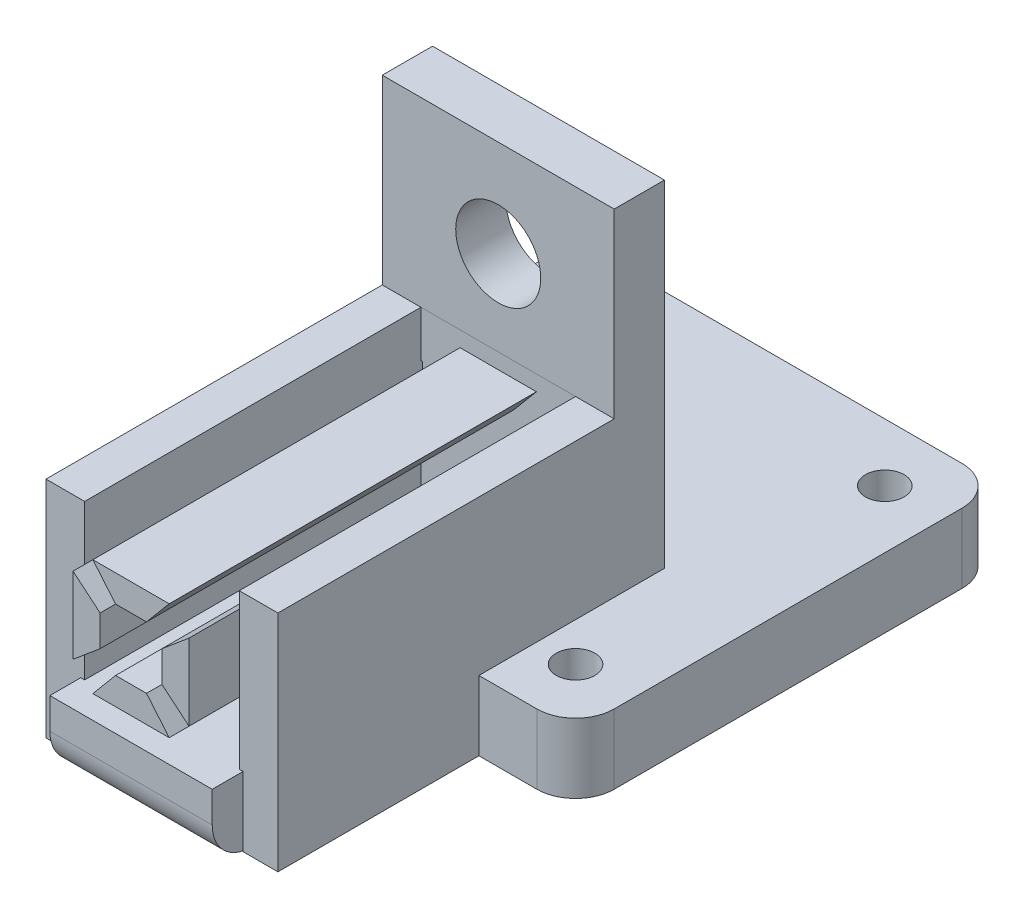
SolidWorks part; units mm, degrees
ref_plane "Front Plane" through (0, 0, 0) normal (0, 0, 1) x (1, 0, 0)
ref_plane "Top Plane" through (0, 0, 0) normal (0, 1, 0) x (1, 0, 0)
ref_plane "Right Plane" through (0, 0, 0) normal (1, 0, 0) x (0, 0, -1)
sketch "Sketch1" plane through (0, 0, 0) normal (0, 1, 0) x (1, 0, 0)
  line L0 (27.5, 55) -> (27.5, 0) construction
  line L1 (5, 0) -> (50, 0)
  line L2 (0, 5) -> (0, 50)
  line L3 (5, 55) -> (50, 55)
  line L4 (55, 5) -> (55, 50)
  line L5 (0, 55) -> (7.5, 55) construction
  line L6 (0, 55) -> (0, 47.5) construction
  line L7 (0, 47.5) -> (7.5, 47.5) construction
  line L8 (7.5, 55) -> (7.5, 47.5) construction
  line L9 (0, 27.5) -> (55, 27.5) construction
  circle A0 centre (7.5, 47.5) radius 2.5
  circle A1 centre (47.5, 47.5) radius 2.5
  circle A2 centre (47.5, 7.5) radius 2.5
  circle A3 centre (7.5, 7.5) radius 2.5
  arc A4 (50, 0) -> (55, 5) centre (50, 5) ccw
  arc A5 (50, 55) -> (55, 50) centre (50, 50) cw
  arc A6 (0, 50) -> (5, 55) centre (5, 50) cw
  arc A7 (5, 0) -> (0, 5) centre (5, 5) cw
  point P23 (55, 55)
  point P29 (0, 0)
  dimension "D3" = 2
  dimension "D5" = 5
  dimension "D1" = 55
  dimension "D2" = 55
  dimension "D4" = 2
extrude "Boss-Extrude2" add sketch "Sketch1" along normal blind 8 and the other way blind 1
sketch "Sketch2" plane through (0, 8, 0) normal (0, 1, 0) x (1, 0, 0)
  line L0 (0, 27.5) -> (55, 27.5)
  line L1 (0, 50) -> (0, 5) construction
  line L2 (55, 5) -> (55, 50) construction
  line L4 (0, 27.5) -> (55, 27.5)
  line L5 (0, 27.5) -> (0, 55)
  line L6 (0, 55) -> (55, 55)
  line L7 (55, 27.5) -> (55, 55)
  dimension "D1" = 27.5
sketch "Sketch5" plane through (0, 8, 0) normal (0, 1, 0) x (1, 0, 0)
  line L0 (27.5, 27.5) -> (27.5, 0)
  line L2 (5, 0) -> (50, 0) construction
  line L3 (27.5, 27.5) -> (27.5, 24)
  line L5 (27.5, 24) -> (23, 24)
  line L6 (27.5, 24) -> (27.5, 17.5)
  line L7 (27.5, 17.5) -> (23, 17.5)
  line L8 (23, 24) -> (23, 17.5)
  line L9 (27.5, 24) -> (32, 24)
  line L10 (27.5, 24) -> (27.5, 17.5)
  line L11 (27.5, 17.5) -> (32, 17.5)
  line L12 (32, 24) -> (32, 17.5)
  dimension "D1" = 3.5
  dimension "D2" = 6.5
  dimension "D3" = 4.5
  dimension "D4" = 4.5
  dimension "D5" = 6.5
extrude "Boss-Extrude3" add sketch "Sketch5" along normal blind 14.5 contours L5 L8 L7 L0 | L12 L9 L0 L11 region at (29.75, 8, -20.75) region at (25.25, 8, -20.75)
sketch "Sketch6" plane through (0, 0, -24) normal (0, 0, -1) x (-1, 0, 0)
  line L0 (-27.5, 8) -> (-27.5, 17)
  line L1 (-32, 8) -> (-23, 8) construction
  circle A0 centre (-27.5, 17) radius 4
  dimension "D2" = 8
  dimension "D1" = 9
extrude "Cut-Extrude4" cut sketch "Sketch6" against normal blind 1.5 contours A0 region at (24.7516, 14.2516, -24)
sketch "Sketch11" plane through (0, 0, -24) normal (0, 0, -1) x (-1, 0, 0)
  line L0 (-27.5, 22.5) -> (-25.5, 22.5)
  line L1 (-32.4368, 26) -> (-22.5632, 26)
  line L2 (-32, 22.5) -> (-23, 22.5) construction
  line L3 (-25.5, 22.5) -> (-27.5, 22.5)
  line L4 (-25.5, 22.5) -> (-29.5, 22.5)
  line L5 (-25.5, 22.5) -> (-25.5, 26)
  line L6 (-25.5, 26) -> (-29.5, 26)
  line L7 (-29.5, 22.5) -> (-29.5, 26)
  line L8 (-22.5632, 26) -> (-25.5, 22.5)
  line L9 (-29.5, 22.5) -> (-32.4368, 26)
  point P10 (-27.5, 26)
  line M9 (-23, 22.5) -> (-32, 22.5)
  dimension "D1" = 2
  dimension "D2" = 4
  dimension "D3" = 3.5
  dimension "D4" = 40
sketch "Sketch12" plane through (0, 8, 0) normal (0, 1, 0) x (1, 0, 0)
  line L0 (27.5, 17.5) -> (27.5, 0)
  line L1 (32, 17.5) -> (23, 17.5) construction
  line L2 (5, 0) -> (50, 0) construction
  line L3 (17, 0) -> (17, -30)
  line L4 (17, 0) -> (38, 0)
  line L5 (27.5, 0) -> (27.5, -30)
  line L6 (17, -30) -> (38, -30)
  line L7 (38, 0) -> (38, -30)
  point P9 (23.9675, 0)
  line M9 (5, 0) -> (50, 0)
  dimension "D1" = 30
  dimension "D2" = 10.5
extrude "Boss-Extrude7" add sketch "Sketch12" against normal blind 9 contours L7 L5 L6 M9 | L3 L6 L5 M9 region at (22.25, 8, 15) region at (32.75, 8, 15)
sketch "Sketch15" plane through (0, 22.5, 0) normal (0, 1, 0) x (1, 0, 0)
  line L0 (32, 24) -> (32, 17.5) construction
  line L1 (32, 17.5) -> (23, 17.5)
  line L2 (32, 17.5) -> (32, 24)
  line L3 (32, 24) -> (23, 24)
  line L4 (23, 17.5) -> (23, 24)
  line L5 (32, 17.5) -> (23, 17.5) construction
extrude "Boss-Extrude8" add sketch "Sketch15" along normal blind 3.5
extrude "Boss-Extrude9" add sketch "Sketch11" against normal blind 54 contours L9 L7 L1 | L7 L5 L1 M9 | L8 L1 L5 region at (27.5, 24.25, -24) region at (24.5211, 24.8333, -24) region at (30.4789, 24.8333, -24)
fillet "Fillet4" radius 5 1 edges at (27.5, -1, 30)
sketch "Sketch18" plane through (0, 26, 0) normal (0, 1, 0) x (1, 0, 0)
  line L0 (32.4368, -30) -> (32.4368, 24) construction
  line L1 (22.5632, 24) -> (32.4368, 24)
  line L2 (22.5632, 24) -> (22.5632, 17.5)
  line L3 (22.5632, 17.5) -> (32.4368, 17.5)
  line L4 (32.4368, 24) -> (32.4368, 17.5)
  dimension "D1" = 6.5
extrude "Boss-Extrude11" add sketch "Sketch18" along normal blind 0.5
sketch "Sketch20" plane through (0, 8, 0) normal (0, 1, 0) x (1, 0, 0)
  line L0 (27.5, -1030) -> (27.5, 48970) construction
  line L1 (17, -30) -> (38, -30) construction
  line L2 (32, 17.5) -> (23, 17.5) construction
  line L3 (27.5, 17.5) -> (16.5, 17.5)
  line L4 (27.5, 17.5) -> (27.5, 0)
  line L5 (27.5, 0) -> (16.5, 0)
  line L6 (16.5, 17.5) -> (16.5, 0)
  line L7 (27.5, 17.5) -> (16.5, 0) construction
  line L8 (27.5, 0) -> (16.5, 17.5) construction
  line L10 (27.5, 17.5) -> (38.5, 17.5)
  line L11 (27.5, 17.5) -> (27.5, 0)
  line L12 (27.5, 0) -> (38.5, 0)
  line L13 (38.5, 17.5) -> (38.5, 0)
  line L14 (27.5, 17.5) -> (38.5, 0) construction
  line L15 (27.5, 0) -> (38.5, 17.5) construction
  line L16 (38.5, 17.5) -> (42.5, 17.5)
  line L17 (38.5, 17.5) -> (38.5, 0)
  line L18 (38.5, 0) -> (42.5, 0)
  line L19 (42.5, 17.5) -> (42.5, 0)
  line L21 (16.5, 17.5) -> (12.5, 17.5)
  line L22 (16.5, 17.5) -> (16.5, 0)
  line L23 (16.5, 0) -> (12.5, 0)
  line L24 (12.5, 17.5) -> (12.5, 0)
  line L26 (42.5, 0) -> (38.5, 0)
  line L27 (42.5, 0) -> (42.5, 17.5)
  line L28 (42.5, 17.5) -> (38.5, 17.5)
  line L29 (38.5, 0) -> (38.5, 17.5)
  line L30 (16.5, 0) -> (12.5, 0)
  line L31 (16.5, 0) -> (16.5, 17.5)
  line L32 (16.5, 17.5) -> (12.5, 17.5)
  line L33 (12.5, 0) -> (12.5, 17.5)
  point P5 (27.5, -30)
  point P9 (22, 8.75)
  point P14 (33, 8.75)
  line M12 (5, 0) -> (17, 0)
  line M16 (38, 0) -> (50, 0)
  dimension "D2" = 11
  dimension "D3" = 17.5
  dimension "D4" = 4
extrude "Boss-Extrude12" add sketch "Sketch20" along normal blind 18 contours L21 L24 L6 M12 | L19 L16 L13 M16 region at (14.5, 8, -8.75) region at (40.5, 8, -8.75)
sketch "Sketch21" plane through (12.5, 0, 0) normal (-1, 0, 0) x (0, 0, 1)
  line L0 (-17.5, 26) -> (-17.5, 8) construction
  line L1 (0, 26) -> (-17.5, 26)
  line L2 (0, 26) -> (0, 24)
  line L3 (0, 24) -> (-17.5, 24)
  line L4 (-17.5, 26) -> (-17.5, 24)
  dimension "D1" = 2
sketch "Sketch22" plane through (12.5, 0, 0) normal (-1, 0, 0) x (0, 0, 1)
  line L1 (-17.5, 24) -> (0, 24)
  line L2 (-17.5, 24) -> (-17.5, 28)
  line L3 (-17.5, 28) -> (0, 28)
  line L4 (0, 24) -> (0, 28)
  dimension "D1" = 4
extrude "Boss-Extrude13" add sketch "Sketch22" along normal blind 11 and the other way blind 4 contours L3 L4 L1 L2
sketch "Sketch25" plane through (0, 28, 0) normal (0, 1, 0) x (1, 0, 0)
  line L2 (1.5, 17.5) -> (16.5, 17.5) construction
  line L3 (1.5, 0) -> (3.5, 0)
  line L4 (1.5, 0) -> (1.5, 17.5)
  line L5 (1.5, 17.5) -> (3.5, 17.5)
  line L6 (3.5, 0) -> (3.5, 17.5)
  dimension "D1" = 2
extrude "Boss-Extrude14" add sketch "Sketch25" along normal blind 41
sketch "Sketch28" plane through (1.5, 0, 0) normal (-1, 0, 0) x (0, 0, 1)
  line L2 (0, 69) -> (-41, 69)
  line L3 (0, 69) -> (0, 24)
  line L4 (0, 24) -> (-41, 24)
  line L5 (-41, 69) -> (-41, 24)
  dimension "D1" = 45
  dimension "D2" = 41
extrude "Boss-Extrude15" add sketch "Sketch28" against normal blind 2
sketch "Sketch29" plane through (1.5, 0, 0) normal (-1, 0, 0) x (0, 0, 1)
  line L1 (0, 24) -> (-5, 24)
  line L2 (0, 24) -> (0, 33)
  line L3 (0, 33) -> (-5, 33)
  line L4 (-5, 24) -> (-5, 33)
  circle A0 centre (-5, 33) radius 1.75
  circle A1 centre (-36, 33) radius 1.75
  circle A2 centre (-36, 64) radius 1.75
  circle A3 centre (-5, 64) radius 1.75
  dimension "D3" = 3.5
  dimension "D6" = 31
  dimension "D1" = 9
  dimension "D2" = 5
  dimension "D7" = 31
  dimension "D4" = 2
  dimension "D5" = 2
extrude "Cut-Extrude8" cut sketch "Sketch29" against normal blind 9 contours A1 | A3 | A0 | A2 region at (1.5, 33, -36) region at (1.5, 64, -5)
sketch "Sketch30" plane through (42.5, 0, 0) normal (1, 0, 0) x (0, 0, -1)
  line L0 (17.5, 26) -> (17.5, 8) construction
  line L1 (0, 26) -> (17.5, 26)
  line L2 (0, 26) -> (0, 24)
  line L3 (0, 24) -> (17.5, 24)
  line L4 (17.5, 26) -> (17.5, 24)
  line L6 (0, 24) -> (17.5, 24)
  line L7 (0, 24) -> (0, 28)
  line L8 (0, 28) -> (17.5, 28)
  line L9 (17.5, 24) -> (17.5, 28)
  line M4 (17.5, 8) -> (17.5, 26)
  line M5 (17.5, 26) -> (0, 26)
  line M6 (0, 26) -> (0, 8)
  dimension "D1" = 2
  dimension "D2" = 4
extrude "Boss-Extrude16" add sketch "Sketch30" along normal blind 9 and the other way blind 4 contours L3 M6 M4 M5 | L9 L8 L7 M5 region at (42.5, 27, -8.75) region at (42.5, 25, -8.75)
sketch "Sketch31" plane through (3.5, 0, 0) normal (1, 0, 0) x (0, 0, -1)
  line L1 (41, 69) -> (20.5, 69)
  line L2 (41, 69) -> (41, 47)
  line L3 (41, 47) -> (20.5, 47)
  line L4 (20.5, 69) -> (20.5, 47)
  circle A0 centre (20.5, 47) radius 10
  dimension "D3" = 20
  dimension "D1" = 22
  dimension "D2" = 20.5
extrude "Cut-Extrude9" cut sketch "Sketch31" against normal blind 9 contours L4 A0 L3 | L3 A0 L4 region at (3.5, 51.2441, -24.7441) region at (3.5, 45.5853, -19.0853)
sketch "Sketch32" plane through (0, 0, -17.5) normal (0, 0, -1) x (-1, 0, 0)
  line L1 (-16.5, 28) -> (-3.5, 28)
  line L2 (-16.5, 28) -> (-16.5, 24)
  line L3 (-16.5, 24) -> (-3.5, 24)
  line L4 (-3.5, 28) -> (-3.5, 24)
extrude "Boss-Extrude17" add sketch "Sketch32" along normal blind 23.5
sketch "Sketch33" plane through (0, 8, 0) normal (0, 1, 0) x (1, 0, 0)
  line L0 (38.5, 17.5) -> (38.5, 0)
  line L1 (38.5, 17.5) -> (38, 17.5)
  line L2 (38.5, 0) -> (38, 0)
  line L3 (38, 17.5) -> (38, 0)
  line L4 (16.5, 17.5) -> (16.5, 0)
  line L5 (16.5, 17.5) -> (17, 17.5)
  line L6 (16.5, 0) -> (17, 0)
  line L7 (17, 17.5) -> (17, 0)
  dimension "D1" = 0.5
  dimension "D2" = 0.5
extrude "Boss-Extrude18" add sketch "Sketch33" along normal blind 20
sketch "Sketch34" plane through (0, 0, 0) normal (0, 0, 1) x (1, 0, 0)
  line L0 (42.5, 24) -> (42.5, 8) construction
  line L1 (51.5, 28) -> (42.5, 28)
  line L2 (51.5, 28) -> (51.5, 24)
  line L3 (51.5, 24) -> (42.5, 24)
  line L4 (42.5, 28) -> (42.5, 24)
  line L5 (42.5, 24) -> (51.5, 24) construction
  line L7 (42.5, 28) -> (38, 28)
  line L8 (42.5, 28) -> (42.5, -1)
  line L9 (42.5, -1) -> (38, -1)
  line L10 (38, 28) -> (38, -1)
  line L11 (17, 28) -> (1.5, 28)
  line L12 (17, 28) -> (17, 24)
  line L13 (17, 24) -> (1.5, 24)
  line L14 (1.5, 28) -> (1.5, 24)
  line L15 (12.5, 24) -> (17, 24)
  line L16 (12.5, 24) -> (12.5, -1)
  line L17 (12.5, -1) -> (17, -1)
  line L18 (17, 24) -> (17, -1)
  line M1 (42.5, 8) -> (42.5, 24)
  line M2 (42.5, 24) -> (51.5, 24)
  line M3 (51.5, 24) -> (51.5, 28)
  line M4 (51.5, 28) -> (38, 28)
  line M5 (38, 28) -> (38, 8)
  line M6 (38, 8) -> (38, -1)
  line M7 (38, -1) -> (50, -1)
extrude "Boss-Extrude19" add sketch "Sketch34" along normal blind 26 contours L18 L13 L16 L17 | L11 L14 L13 L12 | L8 L4 M1 M4 M5 M6 M7 | L4 M4 M2 M3 region at (47, 26, 0) region at (40.25, 13.5, 0) region at (9.25, 26, 0) region at (14.75, 11.5, 0)
sketch "Sketch35" plane through (0, 0, -17.5) normal (0, 0, 1) x (1, 0, 0)
  line L1 (32.4368, 26.5) -> (22.5632, 26.5)
  line L2 (32.4368, 26.5) -> (32.4368, 26)
  line L3 (32.4368, 26) -> (22.5632, 26)
  line L4 (22.5632, 26.5) -> (22.5632, 26)
extrude "Boss-Extrude20" add sketch "Sketch35" along normal blind 47.5
sketch "Sketch37" plane through (0, 0, -17.5) normal (0, 0, 1) x (1, 0, 0)
  line L0 (27.5, 8) -> (29.5, 8)
  line L2 (32, 8) -> (23, 8) construction
  line L3 (29.5, 12) -> (33.1362, 7.6666)
  line L4 (29.5, 8) -> (25.5, 8)
  line L5 (29.5, 8) -> (29.5, 12)
  line L6 (29.5, 12) -> (25.5, 12)
  line L7 (25.5, 8) -> (25.5, 12)
  line L8 (25.5, 12) -> (21.8638, 7.6666)
  line L9 (21.8638, 7.6666) -> (33.1362, 7.6666)
  line M8 (32, 8) -> (32, 25.4794)
  line M12 (23, 25.4794) -> (23, 8)
  line M13 (23, 8) -> (32, 8)
  dimension "D1" = 2
  dimension "D2" = 4
  dimension "D3" = 4
  dimension "D4" = 40
  dimension "D5" = 40
extrude "Boss-Extrude21" add sketch "Sketch37" along normal blind 47.5 contours L7 L8 M12 M13 | L7 L5 L6 M13 | L5 L3 M13 M8 | L8 L9 L3 M8 M13 M12 region at (27.5, 10, -17.5) region at (27.5, 7.9298, -17.5) region at (30.5027, 9.4025, -17.5) region at (24.4973, 9.4025, -17.5)
sketch "Sketch38" plane through (0, 0, 30) normal (0, 0, 1) x (1, 0, 0)
  line L1 (22.5632, 26.5) -> (22.1436, 26.5)
  line L2 (22.5632, 26.5) -> (22.5632, 8)
  line L3 (22.5632, 8) -> (22.1436, 8)
  line L4 (22.1436, 26.5) -> (22.1436, 8)
  line L5 (32.4368, 26.5) -> (32.8564, 26.5)
  line L6 (32.4368, 26.5) -> (32.4368, 8)
  line L7 (32.4368, 8) -> (32.8564, 8)
  line L8 (32.8564, 26.5) -> (32.8564, 8)
extrude "Cut-Extrude10" cut sketch "Sketch38" against normal blind 90.5
sketch "Sketch39" plane through (0, 0, 30) normal (0, 0, 1) x (1, 0, 0)
  line L0 (27.784, 26.1035) -> (27.5, 26.5)
  line L1 (32.4368, 26.5) -> (38, 26.5)
  line L2 (32.4368, 26.5) -> (32.4368, 8)
  line L3 (32.4368, 8) -> (38, 8)
  line L4 (38, 26.5) -> (38, 8)
  line L5 (32.4368, 26.5) -> (22.5632, 26.5) construction
  line L6 (27.5, 26.5) -> (27.5, 8)
  line L7 (38, 17.25) -> (38, 19.25)
  line L8 (34, 19.25) -> (38, 22.6064)
  line L9 (38, 19.25) -> (34, 19.25)
  line L10 (38, 19.25) -> (38, 15.25)
  line L11 (38, 15.25) -> (34, 15.25)
  line L12 (34, 19.25) -> (34, 15.25)
  line L13 (34, 15.25) -> (38, 11.8936)
  line L14 (22.5632, 8.5) -> (21.9673, 8)
  line L15 (17, 8) -> (22.5632, 8) construction
  line L16 (17, 22.6064) -> (17.7151, 22.6064)
  line L17 (38, 22.6064) -> (37.2849, 22.6064)
  line L18 (38, 22.6064) -> (38, 22.0064)
  line L19 (38, 22.0064) -> (37.2849, 22.0064)
  line L20 (37.2849, 22.6064) -> (37.2849, 22.0064)
  line L21 (38, 11.8936) -> (37.2849, 11.8936)
  line L22 (38, 11.8936) -> (38, 12.4936)
  line L23 (38, 12.4936) -> (37.2849, 12.4936)
  line L24 (37.2849, 11.8936) -> (37.2849, 12.4936)
  line L25 (17.7151, 22.6064) -> (17.7151, 22.0064)
  line L26 (17, 22.0064) -> (17.7151, 22.0064)
  line L27 (21, 19.25) -> (17, 22.6064)
  line L28 (21, 19.25) -> (21, 15.25)
  line L29 (17, 19.25) -> (21, 19.25)
  line L30 (17.7151, 11.8936) -> (17.7151, 12.4936)
  line L31 (17, 11.8936) -> (17.7151, 11.8936)
  line L32 (17, 12.4936) -> (17.7151, 12.4936)
  line L33 (17, 26.5) -> (17, 8)
  line L34 (17, 15.25) -> (21, 15.25)
  line L35 (21, 15.25) -> (17, 11.8936)
  line L36 (17, 19.25) -> (17, 22.0064)
  line L37 (17, 22.0064) -> (17.7151, 22.0064)
  line L38 (17.7151, 22.0064) -> (21, 19.25)
  line L39 (17, 19.25) -> (21, 19.25)
  dimension "D1" = 2
  dimension "D2" = 4
  dimension "D3" = 4
  dimension "D4" = 40
  dimension "D5" = 40
  dimension "D6" = 0.6
  dimension "D7" = 0.6
extrude "Boss-Extrude23" add sketch "Sketch39" against normal blind 47.5 contours L26 L33 L29 L27 | L33 L34 L28 L29 | L35 L34 L33 L32 | L23 L4 L11 L13 | L9 L12 L11 L4 | L4 L19 L8 L9 region at (36.6305, 20.3081, 30) region at (36, 17.25, 30) region at (36.6305, 14.1919, 30) region at (18.3695, 20.3081, 30) region at (19, 17.25, 30) region at (18.3695, 14.1919, 30)
ref_plane "Plane1" through (5, 8, 0) normal (0, 1, 0) x (1, 0, 0)
sketch "Sketch48" plane through (0, 8, 0) normal (0, 1, 0) x (1, 0, 0)
  line L1 (7.5, 24) -> (47.5, 24)
  line L3 (7.5, 17.5) -> (47.5, 17.5)
  line L7 (7.5, 17.5) -> (7.5, 24)
  line L15 (47.5, 24) -> (47.5, 17.5)
  line M3 (12.5, 17.5) -> (17, 17.5)
  line M8 (22.5632, 17.5) -> (23, 17.5)
  line M9 (23, 17.5) -> (23, 24)
  line M11 (32, 24) -> (32, 17.5)
  line M12 (32, 17.5) -> (32.4368, 17.5)
  line M17 (38, 17.5) -> (42.5, 17.5)
sketch "Sketch49" plane through (0, 0, -24) normal (0, 0, -1) x (-1, 0, 0)
  line L0 (-17.5, 3.5) -> (-27.5, 17)
  line L1 (-27.5, 17) -> (-17.5, 17)
  line L2 (-17.5, 17) -> (-17.5, 3.5)
  line L3 (-27.5, 17) -> (-37.5, 3.5)
  line L4 (-37.5, 3.5) -> (-37.5, 17)
  line L5 (-37.5, 17) -> (-27.5, 17)
  circle A0 centre (-37.5, 17) radius 4
  circle A1 centre (-17.5, 17) radius 4
  dimension "D1" = 8
  dimension "D2" = 8
extrude "Boss-Extrude31" add sketch "Sketch48" along normal blind 18.5 contours M12 M17 M11 | L15 | M8 M9 M3 | L7 region at (15.25, 8, -20.75) region at (39.75, 8, -20.75)
sketch "Sketch51" plane through (0, 0, -24) normal (0, 0, -1) x (-1, 0, 0)
  line L1 (-32.4593, 12.5515) -> (-22.8331, 12.5515)
  line L2 (-32.4593, 12.5515) -> (-32.4593, 21.6767)
  line L3 (-32.4593, 21.6767) -> (-22.8331, 21.6767)
  line L4 (-22.8331, 12.5515) -> (-22.8331, 21.6767)
extrude "Boss-Extrude32" add sketch "Sketch51" against normal blind 1.5
sketch "Sketch53" plane through (0, 0, -24) normal (0, 0, -1) x (-1, 0, 0)
  line L0 (-27.5, 17) -> (-27.5, 8)
  line L1 (-47.5, 8) -> (-7.5, 8) construction
  line L2 (-27.5, 8) -> (-27.5, 26.5)
  line L3 (-47.5, 26.5) -> (-16.5, 26.5) construction
  line L4 (-27.5, 17.25) -> (-23.5, 17.25)
  line L5 (-23.5, 17.25) -> (-31.5, 17.25)
  line L7 (-31.5, 13.25) -> (-23.5, 13.25)
  line L8 (-31.5, 13.25) -> (-31.5, 21.25)
  line L9 (-31.5, 21.25) -> (-23.5, 21.25)
  line L10 (-23.5, 13.25) -> (-23.5, 21.25)
  line L11 (-31.5, 13.25) -> (-23.5, 21.25) construction
  line L12 (-31.5, 21.25) -> (-23.5, 13.25) construction
  dimension "D1" = 4
  dimension "D2" = 4
  dimension "D3" = 8
  dimension "D4" = 8
sketch "Sketch54" plane through (0, 0, -17.5) normal (0, 0, 1) x (1, 0, 0)
  line L0 (27.5, 22.5) -> (27.5, 14.5)
  line L1 (29.5, 22.5) -> (25.5, 22.5) construction
  line L3 (23.5, 22.5) -> (31.5, 22.5)
  line L4 (23.5, 22.5) -> (23.5, 14.5)
  line L5 (23.5, 14.5) -> (31.5, 14.5)
  line L6 (31.5, 22.5) -> (31.5, 14.5)
  line L7 (23.5, 22.5) -> (31.5, 14.5) construction
  line L8 (23.5, 14.5) -> (31.5, 22.5) construction
  point P4 (27.5, 18.5)
  line M17 (29.5, 22.5) -> (25.5, 22.5)
  dimension "D1" = 8
  dimension "D2" = 8
  dimension "D3" = 8
extrude "Boss-Extrude35" add sketch "Sketch54" along normal blind 47.5 contours L6 L3 L0 L5 M17 | L4 L5 L0 L3 M17 region at (29.5, 18.5, -17.5) region at (25.5, 18.5, -17.5)
sketch "Sketch55" plane through (0, 0, 30) normal (0, 0, 1) x (1, 0, 0)
  line L1 (32.4368, 26.5) -> (22.5632, 26.5)
  line L2 (32.4368, 26.5) -> (32.4368, 26)
  line L3 (32.4368, 26) -> (22.5632, 26)
  line L4 (22.5632, 26.5) -> (22.5632, 26)
extrude "Cut-Extrude12" cut sketch "Sketch55" against normal blind 47.5
sketch "Sketch56" plane through (0, 0, 26) normal (0, 0, 1) x (1, 0, 0)
  line L1 (38, 28) -> (37.5, 28)
  line L2 (38, 28) -> (38, 8)
  line L3 (38, 8) -> (37.5, 8)
  line L4 (37.5, 28) -> (37.5, 8)
  line L5 (17, 28) -> (17.5, 28)
  line L6 (17, 28) -> (17, 8)
  line L7 (17, 8) -> (17.5, 8)
  line L8 (17.5, 28) -> (17.5, 8)
  dimension "D1" = 0.5
  dimension "D2" = 0.5
extrude "Boss-Extrude36" add sketch "Sketch56" against normal blind 43.5
sketch "Sketch57" plane through (0, 0, 30) normal (0, 0, 1) x (1, 0, 0)
  line L0 (31.5, 20.5) -> (31.5, 16.5)
  line L1 (35, 18.4644) -> (35, 13.5632)
  line L2 (25.5, 22.5) -> (29.5, 22.5)
  line L3 (29.5, 22.5) -> (32.4368, 26)
  line L4 (29.5, 22.5) -> (29.5, 26)
  line L5 (22.5632, 26) -> (32.4368, 26) construction
  line L6 (31.5, 22.5) -> (31.5, 14.5) construction
  line L7 (35, 13.5632) -> (31.5, 16.5)
  line L8 (31.5, 16.5) -> (35, 16.5)
  line L9 (31.5, 16.5) -> (31.5, 20.4288)
  line L10 (31.5, 20.4288) -> (35, 20.4288)
  line L11 (35, 16.5) -> (35, 20.4288)
  line L12 (35, 18.5356) -> (35, 23.4368)
  line L13 (35, 16.5) -> (31.5, 16.5)
  line L14 (35, 16.5) -> (35, 18.5)
  line L15 (35, 18.5) -> (31.5, 18.5)
  line L16 (31.5, 16.5) -> (31.5, 18.5)
  line L17 (35, 23.4368) -> (31.5, 20.5)
  line L18 (27.5, 22.5) -> (27.5, 14.5) construction
  line L19 (23.5, 14.5) -> (31.5, 14.5) construction
  line L20 (20, 13.5632) -> (23.5, 16.5)
  line L21 (23.5, 16.5) -> (20, 16.5)
  line L22 (20, 18.4644) -> (20, 13.5632)
  line L23 (20, 18.5356) -> (20, 23.4368)
  line L24 (20, 23.4368) -> (23.5, 20.5)
  line L25 (23.5, 20.5) -> (23.5, 16.5)
  line L26 (27.5, 18.5) -> (31.5, 18.5) construction
  line L27 (31.5, 18.5) -> (23.5, 18.5) construction
  line L28 (23.5, 20.5) -> (23.5, 16.5)
  line L29 (32.4368, 26) -> (22.5632, 26)
  line L30 (22.5632, 26) -> (25.5, 22.5)
  line L31 (25.5, 14.5) -> (29.5, 14.5)
  line L32 (22.5632, 11) -> (25.5, 14.5)
  line L33 (32.4368, 11) -> (22.5632, 11)
  line L34 (29.5, 14.5) -> (32.4368, 11)
  line L35 (23.5, 16.5) -> (20, 13.5632)
  line L36 (20, 13.5632) -> (20, 23.4368)
  line L37 (20, 23.4368) -> (23.5, 20.5)
  line L38 (23.5, 18.5) -> (23.5, 20.5)
  line M12 (23.5, 22.5) -> (23.5, 14.5)
  line M13 (23.5, 14.5) -> (31.5, 14.5)
  line M14 (31.5, 14.5) -> (31.5, 22.5)
  dimension "D1" = 2
  dimension "D2" = 3.5
  dimension "D3" = 130
extrude "Boss-Extrude37" add sketch "Sketch57" against normal blind 47.5 contours L12 L17 L0 L10 | L15 L11 L10 L9 | L11 L15 L8 L1 M14 | L8 L7 L1 | L34 L32 L33 M13 | L36 L22 L21 L28 L24 L23 M12 | L21 L22 L20 region at (33.8064, 21.432, 30) region at (21.1667, 15.5211, 30) region at (21.5934, 19.2999, 30) region at (27.5, 12.503, 30) region at (33.25, 19.4644, 30) region at (33.25, 17.5, 30) region at (33.8333, 15.5211, 30)
sketch "Sketch58" plane through (0, 0, 30) normal (0, 0, 1) x (1, 0, 0)
  line L1 (38, 22.0064) -> (37.2849, 22.0064)
  line L2 (38, 22.0064) -> (38, 12.4936)
  line L3 (38, 12.4936) -> (37.2849, 12.4936)
  line L4 (37.2849, 22.0064) -> (37.2849, 12.4936)
  line L5 (17, 22.0064) -> (17.7151, 22.0064)
  line L6 (17, 22.0064) -> (17, 12.4936)
  line L7 (17, 12.4936) -> (17.7151, 12.4936)
  line L8 (17.7151, 22.0064) -> (17.7151, 12.4936)
extrude "Cut-Extrude13" cut sketch "Sketch58" against normal blind 4
sketch "Sketch59" plane through (0, 0, 30) normal (0, 0, 1) x (1, 0, 0)
  line L0 (37.2849, 22.0064) -> (35, 20.0891)
  line L1 (35, 20.0891) -> (35, 14.4109)
  line L2 (35, 14.4109) -> (37.2849, 12.4936)
  line L3 (37.2849, 12.4936) -> (37.2849, 22.0064)
  line L4 (17.7151, 22.0064) -> (20, 20.0891)
  line L5 (20, 20.0891) -> (20, 14.4109)
  line L6 (20, 14.4109) -> (17.7151, 12.4936)
  line L7 (20, 14.4109) -> (17.7151, 12.4936) construction
  line L8 (17.7151, 12.4936) -> (17.7151, 22.0064)
extrude "Cut-Extrude15" cut sketch "Sketch59" against normal blind 47.5
sketch "Sketch60" plane through (0, 0, 26) normal (0, 0, 1) x (1, 0, 0)
  line L0 (17.7151, 12.4936) -> (17.7151, 22.0064) construction
  line L1 (37.2849, 22.0064) -> (37.5, 22.0064)
  line L2 (37.2849, 22.0064) -> (37.2849, 12.4936)
  line L3 (37.2849, 12.4936) -> (37.5, 12.4936)
  line L4 (37.5, 22.0064) -> (37.5, 12.4936)
  line L5 (17.5, 22.0064) -> (17.7151, 22.0064)
  line L6 (17.5, 22.0064) -> (17.5, 12.4936)
  line L7 (17.5, 12.4936) -> (17.7151, 12.4936)
  line L8 (17.7151, 22.0064) -> (17.7151, 12.4936)
extrude "Cut-Extrude16" cut sketch "Sketch60" against normal blind 47.5
sketch "Sketch61" plane through (0, 0, 30) normal (0, 0, 1) x (1, 0, 0)
  line L0 (32.4368, 8) -> (22.5632, 8)
  line L1 (22.5632, 8) -> (22.5632, 8.5)
  line L2 (22.5632, 8.5) -> (24.6609, 11)
  line L3 (24.6609, 11) -> (30.3391, 11)
  line L4 (30.3391, 11) -> (32.4368, 8.5)
  line L5 (32.4368, 8.5) -> (32.4368, 8)
extrude "Cut-Extrude17" cut sketch "Sketch61" against normal blind 47.5
sketch "Sketch62" plane through (0, 0, 30) normal (0, 0, 1) x (1, 0, 0)
  line L1 (23.5, 22.5) -> (31.5, 22.5)
  line L2 (23.5, 22.5) -> (23.5, 14.5)
  line L3 (23.5, 14.5) -> (31.5, 14.5)
  line L4 (31.5, 22.5) -> (31.5, 14.5)
extrude "Cut-Extrude18" cut sketch "Sketch62" against normal blind 47.5
sketch "Sketch63" plane through (0, 0, -41) normal (0, 0, -1) x (-1, 0, 0)
  line L1 (-3.5, 28) -> (-16.5, 28)
  line L2 (-3.5, 28) -> (-3.5, 24)
  line L3 (-3.5, 24) -> (-16.5, 24)
  line L4 (-16.5, 28) -> (-16.5, 24)
extrude "Cut-Extrude20" cut sketch "Sketch63" against normal blind 17
sketch "Sketch64" plane through (0, 0, -17.5) normal (0, 0, -1) x (-1, 0, 0)
  line L1 (-17.5, 26.5) -> (-16.5, 26.5)
  line L2 (-17.5, 26.5) -> (-17.5, 28)
  line L3 (-17.5, 28) -> (-16.5, 28)
  line L4 (-16.5, 26.5) -> (-16.5, 28)
extrude "Boss-Extrude38" add sketch "Sketch64" along normal blind 6.5
sketch "Sketch68" plane through (0, 0, -41) normal (0, 0, -1) x (-1, 0, 0)
  line L1 (-1.5, 69) -> (-3.5, 69)
  line L2 (-1.5, 69) -> (-1.5, 24)
  line L3 (-1.5, 24) -> (-3.5, 24)
  line L4 (-3.5, 69) -> (-3.5, 24)
extrude "Cut-Extrude23" cut sketch "Sketch68" against normal blind 17
sketch "Sketch69" plane through (0, 0, -24) normal (0, 0, -1) x (-1, 0, 0)
  line L1 (-3.5, 28) -> (-1.5, 28)
  line L2 (-3.5, 28) -> (-3.5, 69)
  line L3 (-3.5, 69) -> (-1.5, 69)
  line L4 (-1.5, 28) -> (-1.5, 69)
extrude "Cut-Extrude24" cut sketch "Sketch69" against normal blind 37
sketch "Sketch70" plane through (0, 0, -24) normal (0, 0, -1) x (-1, 0, 0)
  line L1 (-17.5, 26.5) -> (-1.5, 26.5)
  line L2 (-17.5, 26.5) -> (-17.5, 28)
  line L3 (-17.5, 28) -> (-1.5, 28)
  line L4 (-1.5, 26.5) -> (-1.5, 28)
  line L5 (-7.5, 24) -> (-1.5, 24)
  line L6 (-7.5, 24) -> (-7.5, 26.5)
  line L7 (-7.5, 26.5) -> (-1.5, 26.5)
  line L8 (-1.5, 24) -> (-1.5, 26.5)
  line M3 (-1.5, 24) -> (-1.5, 28)
  line M10 (-7.5, 24) -> (-1.5, 24)
extrude "Cut-Extrude25" cut sketch "Sketch70" against normal blind 6.5 contours L6 L1 M10 M3 | L1 L2 L3 L4 region at (4.5, 25.25, -24)
sketch "Sketch72" plane through (1.5, 0, 0) normal (-1, 0, 0) x (0, 0, 1)
  line L1 (-17.5, 28) -> (26, 28)
  line L2 (-17.5, 28) -> (-17.5, 24)
  line L3 (-17.5, 24) -> (26, 24)
  line L4 (26, 28) -> (26, 24)
extrude "Cut-Extrude26" cut sketch "Sketch72" against normal blind 11
sketch "Sketch73" plane through (51.5, 0, 0) normal (1, 0, 0) x (0, 0, -1)
  line L1 (17.5, 28) -> (-26, 28)
  line L2 (17.5, 28) -> (17.5, 24)
  line L3 (17.5, 24) -> (-26, 24)
  line L4 (-26, 28) -> (-26, 24)
extrude "Cut-Extrude27" cut sketch "Sketch73" against normal blind 9
sketch "Sketch74" plane through (7.5, 0, 0) normal (-1, 0, 0) x (0, 0, 1)
  line L1 (-24, 26.5) -> (-17.5, 26.5)
  line L2 (-24, 26.5) -> (-24, 8)
  line L3 (-24, 8) -> (-17.5, 8)
  line L4 (-17.5, 26.5) -> (-17.5, 8)
extrude "Cut-Extrude28" cut sketch "Sketch74" against normal blind 5
sketch "Sketch75" plane through (47.5, 0, 0) normal (1, 0, 0) x (0, 0, -1)
  line L1 (24, 26.5) -> (17.5, 26.5)
  line L2 (24, 26.5) -> (24, 8)
  line L3 (24, 8) -> (17.5, 8)
  line L4 (17.5, 26.5) -> (17.5, 8)
extrude "Cut-Extrude30" cut sketch "Sketch75" against normal blind 5
sketch "Sketch76" plane through (0, 26.5, 0) normal (0, 1, 0) x (1, 0, 0)
  line L1 (12.5, 24) -> (42.5, 24)
  line L2 (12.5, 24) -> (12.5, 17.5)
  line L3 (12.5, 17.5) -> (42.5, 17.5)
  line L4 (42.5, 24) -> (42.5, 17.5)
extrude "Boss-Extrude39" add sketch "Sketch76" along normal blind 1.5
sketch "Sketch81" plane through (0, 28, 0) normal (0, 1, 0) x (1, 0, 0)
  line L0 (42.5, 24) -> (42.5, -26) construction
  line L1 (12.5, 24) -> (42.5, 24)
  line L2 (12.5, 24) -> (12.5, 17.4984)
  line L3 (12.5, 17.4984) -> (42.5, 17.4984)
  line L4 (42.5, 24) -> (42.5, 17.4984)
extrude "Boss-Extrude44" add sketch "Sketch81" along normal blind 23.5
sketch "Sketch82" plane through (0, 0, -24) normal (0, 0, -1) x (-1, 0, 0)
  line L0 (-20, 46.5) -> (-35, 31.5) construction
  line L1 (-35, 46.5) -> (-20, 46.5)
  line L2 (-35, 46.5) -> (-35, 31.5)
  line L3 (-35, 31.5) -> (-20, 31.5)
  line L4 (-20, 46.5) -> (-20, 31.5)
  line L5 (-42.5, 51.5) -> (-12.5, 51.5) construction
  line L6 (-20, 39) -> (-12.5, 39) construction
  line L7 (-12.5, 51.5) -> (-12.5, 8) construction
  line L8 (-35, 39) -> (-42.5, 39) construction
  line L9 (-42.5, 8) -> (-42.5, 51.5) construction
  line L10 (-20, 31.5) -> (-35, 46.5) construction
  circle A0 centre (-33.5, 45) radius 1.5
  circle A1 centre (-21.5, 45) radius 1.5
  circle A2 centre (-21.5, 33) radius 1.5
  circle A3 centre (-33.5, 33) radius 1.5
  circle A4 centre (-27.5, 39) radius 5.5
  point P16 (-27.5, 39)
  point P19 (0, 0)
  point P26 (-27.5, 39)
  point P27 (-27.5, 39)
  dimension "D4" = 4
  dimension "D5" = 11
  dimension "D6" = 3
  dimension "D1" = 5
  dimension "D2" = 15
  dimension "D3" = 15
extrude "Cut-Extrude31" cut sketch "Sketch82" against normal blind 5 contours A0 | A2 | A1 | A3
extrude "Cut-Extrude32" cut sketch "Sketch82<4>" against normal up to next contours A4
sketch "Sketch82<4>" plane through (0, 0, -24) normal (0, 0, -1) x (-1, 0, 0) same geometry as "Sketch82"
